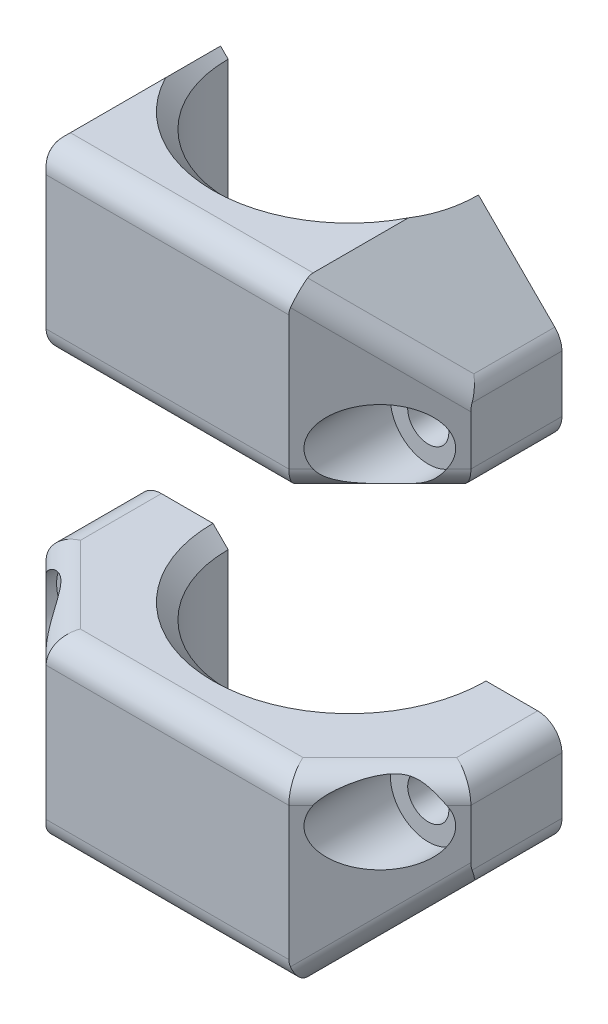
SolidWorks part; units mm, degrees
ref_plane "Front Plane" through (0, 0, 0) normal (0, 0, 1) x (1, 0, 0)
ref_plane "Top Plane" through (0, 0, 0) normal (0, 1, 0) x (1, 0, 0)
ref_plane "Right Plane" through (0, 0, 0) normal (1, 0, 0) x (0, 0, -1)
sketch "Sketch1" plane through (0, 0, 0) normal (0, 0, 1) x (1, 0, 0)
  line L6 (22.225, -12.7) -> (-22.225, -12.7)
  line L7 (22.225, -22.225) -> (22.225, -12.7)
  line L8 (12.7, -31.75) -> (22.225, -22.225)
  line L9 (-12.7, -31.75) -> (12.7, -31.75)
  line L10 (-22.225, -22.225) -> (-12.7, -31.75)
  line L11 (-22.225, -12.7) -> (-22.225, -22.225)
  line L12 (22.225, -12.7) -> (-22.225, -12.7)
  line L13 (22.225, -22.225) -> (22.225, -12.7)
  line L14 (12.7, -31.75) -> (22.225, -22.225)
  line L15 (-12.7, -31.75) -> (12.7, -31.75)
  line L16 (-22.225, -22.225) -> (-12.7, -31.75)
  line L17 (-22.225, -12.7) -> (-22.225, -22.225)
  line L18 (-22.225, 22.225) -> (-22.225, 12.7)
  line L19 (-12.7, 31.75) -> (-22.225, 22.225)
  line L20 (12.7, 31.75) -> (-12.7, 31.75)
  line L21 (22.225, 22.225) -> (12.7, 31.75)
  line L22 (22.225, 12.7) -> (22.225, 22.225)
  line L23 (-22.225, 12.7) -> (22.225, 12.7)
  line L24 (-22.225, 22.225) -> (-22.225, 12.7)
  line L25 (-12.7, 31.75) -> (-22.225, 22.225)
  line L26 (12.7, 31.75) -> (-12.7, 31.75)
  line L27 (22.225, 22.225) -> (12.7, 31.75)
  line L28 (22.225, 12.7) -> (22.225, 22.225)
  line L29 (-22.225, 12.7) -> (22.225, 12.7)
  dimension "D1" = 0
  dimension "D2" = 0
extrude "Boss-Extrude1" add sketch "Sketch1" along normal blind 19.05
sketch "Sketch2" plane through (0, 31.75, 0) normal (0, 1, 0) x (0, 0, 1)
  line L0 (0, -12.7) -> (0, 12.7) construction
  circle A0 centre (0, 0) radius 12.7
  dimension "D1" = 25.4
extrude "Cut-Extrude1" cut sketch "Sketch2" against normal through all both and the other way through all
chamfer "Chamfer1" distance 9.525 angle 45 2 edges at (22.225, 17.4625, 19.05) (-22.225, 17.4625, 19.05)
chamfer "Chamfer2" distance 9.525 angle 45 2 edges at (22.225, -17.4625, 19.05) (-22.225, -17.4625, 19.05)
chamfer "Chamfer3" distance 1.5875 angle 45 2 edges at (0, -12.7, 12.7) (0, -31.75, 12.7)
chamfer "Chamfer4" distance 1.5875 angle 45 2 edges at (0, 31.75, 12.7) (0, 12.7, 12.7)
fillet "Fillet1" radius 2.54 10 edges at (-17.4625, -26.9875, 14.2875) (17.4625, -26.9875, 14.2875) (0, -31.75, 19.05) (-17.4625, -12.7, 14.2875) (0, -12.7, 19.05) (17.4625, -12.7, 14.2875) (22.225, -22.225, 4.7625) (22.225, -12.7, 4.7625) (-22.225, -12.7, 4.7625) (-22.225, -22.225, 4.7625)
fillet "Fillet2" radius 2.54 10 edges at (17.4625, 26.9875, 14.2875) (0, 31.75, 19.05) (-17.4625, 26.9875, 14.2875) (-22.225, 22.225, 4.7625) (-22.225, 12.7, 4.7625) (-17.4625, 12.7, 14.2875) (0, 12.7, 19.05) (17.4625, 12.7, 14.2875) (22.225, 12.7, 4.7625) (22.225, 22.225, 4.7625)
hole_wizard "CBORE for #6 Binding Head Machine Screw1" positions "Sketch3" profile "Sketch4" counterbore size "#6" standard "ANSI Inch"
sketch "Sketch3" plane through (0, 0, 19.05) normal (0, 0, 1) x (1, 0, 0)
  point P1 (-17.4625, 17.1175)
  point P4 (-17.4625, -17.1175)
  point P7 (17.4625, 17.1175)
  point P10 (17.4625, -17.1175)
sketch "Sketch4" plane through (-17.4625, 17.1175, 19.05) normal (1, 0, 0) x (0, -1, 0)
  line L0 (0, 0) -> (0, 23.6454)
  line L1 (0, 23.6454) -> (2.1526, 22.352)
  line L2 (2.1526, 22.352) -> (2.1526, 9.8298)
  line L3 (2.1526, 9.8298) -> (3.9687, 9.8298)
  line L4 (3.9687, 9.8298) -> (3.9688, 0)
  line L5 (3.9688, 0) -> (0, 0)
  line L10 (0, 23.6454) -> (-2.1527, 22.352) construction
  line L11 (0, -6.35) -> (0, 107.95) construction
  dimension "Hole Dia." = 4.3053
  dimension "Hole Depth" = 22.352
  dimension "C'Bore Dia." = 7.9375
  dimension "C'Bore Depth" = 9.8298
  dimension "Drill Angle" = 118
